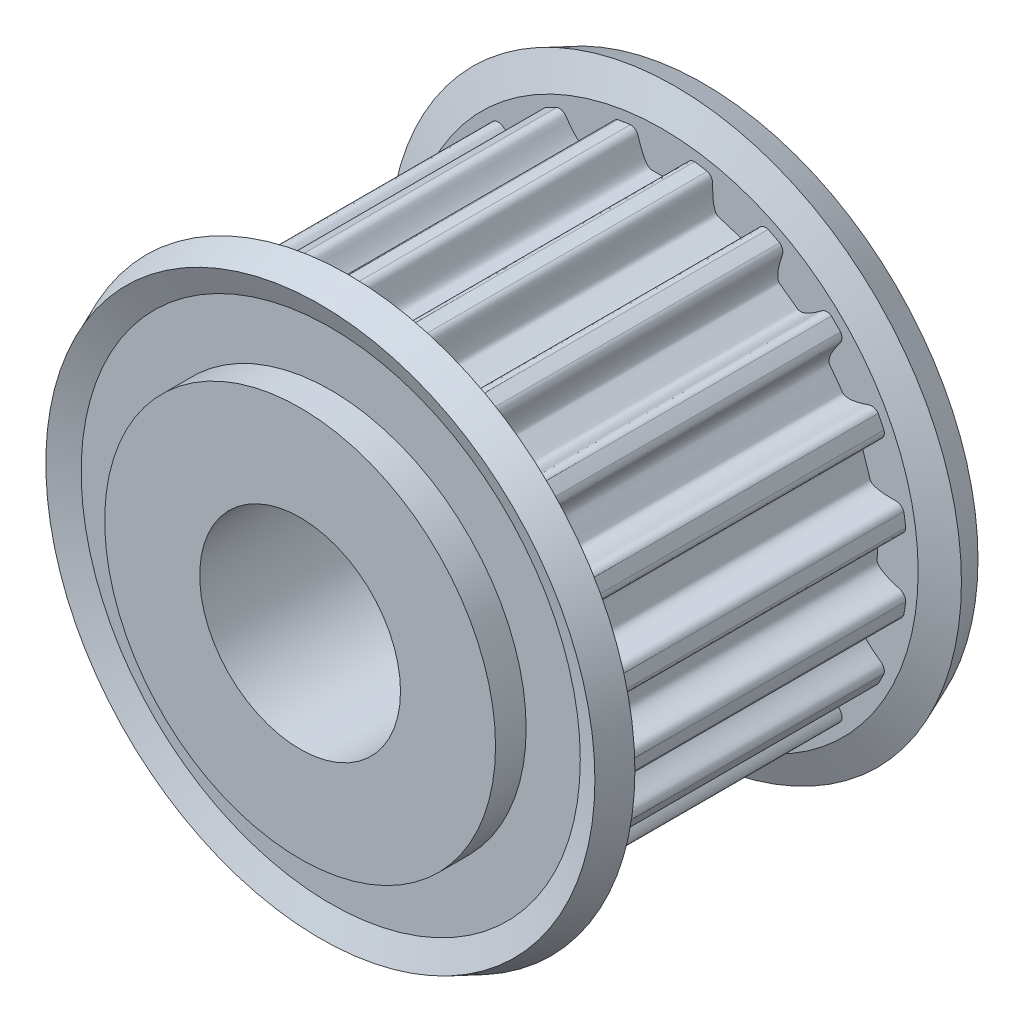
SolidWorks part; units mm, degrees
ref_plane "前视基准面" through (0, 0, 0) normal (0, 0, 1) x (1, 0, 0)
ref_plane "上视基准面" through (0, 0, 0) normal (0, 1, 0) x (1, 0, 0)
ref_plane "右视基准面" through (0, 0, 0) normal (1, 0, 0) x (0, 0, -1)
ref_axis "基准轴1" through (0, 0, 31.1326) along (0, 0, -1)
sketch "SketchRevolveGearBelt01" plane through (0, 0, 0) normal (1, 0, 0) x (0, 0, -1)
  line L0 (0, 0) -> (1, 0) construction
  line L1 (5.274, 0) -> (5.274, 4.8662)
  line L2 (5.274, 4.8662) -> (4.512, 4.8662)
  line L3 (4.512, 4.8662) -> (4.512, 6.2146)
  line L4 (4.512, 6.2146) -> (4.7696, 6.8366)
  line L5 (4.7696, 6.8366) -> (4.0656, 7.1282)
  line L6 (4.0656, 7.1282) -> (3.75, 6.3662)
  line L7 (3.75, 6.3662) -> (3.75, 6.1101)
  line L8 (3.75, 6.1101) -> (-3.75, 6.1101)
  line L9 (-3.75, 6.1101) -> (-3.75, 6.3662)
  line L10 (-3.75, 6.3662) -> (-4.0656, 7.1282)
  line L11 (-4.0656, 7.1282) -> (-4.7696, 6.8366)
  line L12 (-4.7696, 6.8366) -> (-4.512, 6.2146)
  line L13 (-4.512, 6.2146) -> (-4.512, 4.8662)
  line L14 (-4.512, 4.8662) -> (-5.274, 4.8662)
  line L15 (-5.274, 4.8662) -> (-5.274, 0)
  line L16 (-5.274, 0) -> (5.274, 0)
  dimension "GearBeltFlange1OutsideLength" = 1.3484
  dimension "GearBeltFlange1X" = 0.2576
  dimension "GearBeltFlange1Y" = 0.622
  dimension "GearBeltFlangeThickness" = 0.762
  dimension "GearBeltFlangeInside" = 0.2561
  dimension "GearBeltOutsideDiameter" = 6.1101
  dimension "GearBeltFlange2X" = 0.2576
revolve "GearBelt01" add sketch "SketchRevolveGearBelt01" angle 360 about L0
sketch "SketchToothGearBelt01" plane through (0, 0, 0) normal (0, 0, 1) x (1, 0, 0)
  arc A0 (6.0575, 0.8121) -> (6.0575, -0.8121) centre (0, 0) cw
  spline S0 degree 3 poles (6.0575, -0.8121) (6.0583, -0.7986) (6.0575, -0.7783) (6.0524, -0.7518) (6.0465, -0.7324) (6.0388, -0.7137) (6.0292, -0.6958) (6.0178, -0.6791) (6.0048, -0.6635) (5.9903, -0.6494) (5.9744, -0.6368) (5.9573, -0.6259) (5.9393, -0.6166) (5.9014, -0.6028) (5.8513, -0.5872) (5.7909, -0.5675) (5.7401, -0.5498) (5.6924, -0.5322) (5.6478, -0.5145) (5.6062, -0.4969) (5.5678, -0.4793) (5.5323, -0.4616) (5.5, -0.444) (5.4707, -0.4264) (5.4445, -0.4087) (5.4213, -0.3911) (5.4012, -0.3734) (5.3842, -0.3558) (5.3702, -0.3381) (5.3592, -0.3203) (5.3514, -0.3025) (5.3465, -0.2846) (5.3443, -0.2503) (5.3481, -0.2) (5.3485, -0.1333) (5.3495, -0.0666) (5.3497, 0) (5.3495, 0.0666) (5.3485, 0.1333) (5.3481, 0.2) (5.3443, 0.2503) (5.3465, 0.2846) (5.3514, 0.3025) (5.3592, 0.3203) (5.3702, 0.3381) (5.3842, 0.3558) (5.4012, 0.3734) (5.4213, 0.3911) (5.4445, 0.4087) (5.4707, 0.4264) (5.5, 0.444) (5.5323, 0.4616) (5.5678, 0.4793) (5.6062, 0.4969) (5.6478, 0.5145) (5.6924, 0.5322) (5.7401, 0.5498) (5.7909, 0.5675) (5.8513, 0.5872) (5.9014, 0.6028) (5.9393, 0.6166) (5.9573, 0.6259) (5.9744, 0.6368) (5.9903, 0.6494) (6.0048, 0.6635) (6.0178, 0.6791) (6.0292, 0.6958) (6.0388, 0.7137) (6.0465, 0.7324) (6.0524, 0.7518) (6.0575, 0.7783) (6.0583, 0.7986) (6.0575, 0.8121) knots 0 0 0 0 0.016481 0.024721 0.032961 0.041201 0.049442 0.057682 0.065922 0.074162 0.082403 0.090643 0.098883 0.107123 0.13988 0.162959 0.184851 0.205564 0.225106 0.24349 0.260727 0.276834 0.291831 0.305741 0.318596 0.330433 0.341302 0.351266 0.360409 0.368837 0.376686 0.384125 0.391349 0.41855 0.4457 0.47285 0.5 0.52715 0.5543 0.58145 0.608651 0.615875 0.623314 0.631163 0.639591 0.648734 0.658698 0.669567 0.681404 0.694259 0.708169 0.723166 0.739273 0.75651 0.774894 0.794436 0.815149 0.837041 0.86012 0.892877 0.901117 0.909357 0.917597 0.925838 0.934078 0.942318 0.950558 0.958799 0.967039 0.975279 0.983519 1 1 1 1
extrude "ToothExtrudeCutGearBelt01" cut sketch "SketchToothGearBelt01" against normal blind 3.75 and the other way blind 3.75
pattern_circular "PatternGearBelt01" count 20 every 18 about axis through (0, 0, 31.1326) along (0, 0, -1) of "ToothExtrudeCutGearBelt01"
sketch "BoreRevolveSketch" plane through (0, 0, 0) normal (1, 0, 0) x (0, 0, -1)
  line L0 (0, 0) -> (1, 0) construction
  line L1 (-5.274, 0) -> (5.274, 0)
  line L2 (5.274, 0) -> (5.274, 2.5)
  line L3 (5.274, 2.5) -> (-5.274, 2.5)
  line L4 (-5.274, 2.5) -> (-5.274, 0)
  dimension "TaperSide1" = 2.5
  dimension "TaperSide2" = 2.5
revolve "BoreRevolveCut" cut sketch "BoreRevolveSketch" angle 360 about L0
sketch "AuxiliarySketchGearBelt01" plane through (0, 0, 0) normal (0, 0, 1) x (1, 0, 0)
  circle A0 centre (0, 0) radius 6.3662 construction
  dimension "PitchDiameter" = 12.7324
